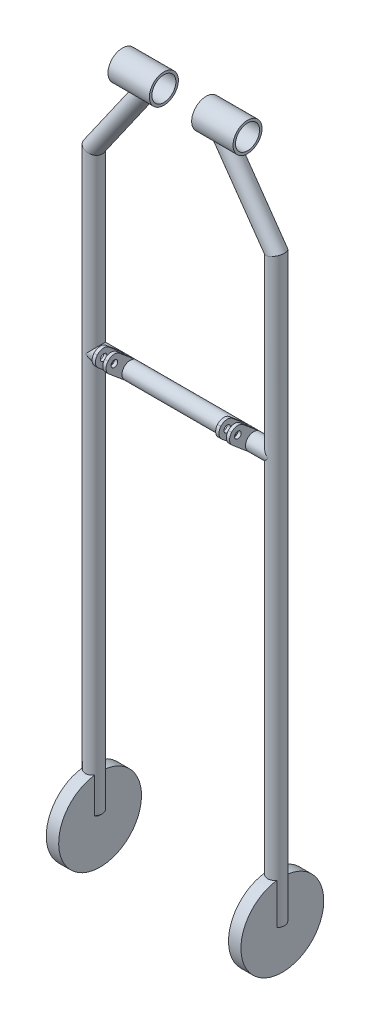
SolidWorks part; units mm, degrees
ref_plane "Alzado" through (0, 0, 0) normal (0, 0, 1) x (1, 0, 0)
ref_plane "Planta" through (0, 0, 0) normal (0, 1, 0) x (1, 0, 0)
ref_plane "Vista lateral" through (0, 0, 0) normal (1, 0, 0) x (0, 0, -1)
sketch "Croquis1" plane through (0, 0, 0) normal (1, 0, 0) x (0, 0, -1)
  circle A0 centre (0, 0) radius 17.5
  circle A1 centre (0, 0) radius 14.5
  dimension "D1" = 35
  dimension "D2" = 3
extrude "Saliente-Extruir1" add sketch "Croquis1" along normal blind 50
sketch "Croquis2" plane through (0, 0, 0) normal (0, 0, 1) x (1, 0, 0)
  line L0 (25, -17.5) -> (-34.5176, -102.5)
  line L1 (-34.5176, -102.5) -> (-34.5176, -802.5)
  line L2 (-34.5176, -102.5) -> (29.5486, -102.5) construction
  line L3 (25, 17.5) -> (25, -17.5) construction
  line L4 (50, 17.5) -> (0, 17.5) construction
  line L5 (0, -17.5) -> (50, -17.5) construction
  line L6 (0, 0) -> (50, 0) construction
  line L7 (50, -17.5) -> (50, 17.5) construction
  dimension "D1" = 85
  dimension "D2" = 700
  dimension "D3" = 55
  dimension "D4" = 64.0663
ref_plane "Plano1" through (25, -17.5, 0) normal (-0.5736, -0.8192, 0) x (0, 0, 1)
sketch "Croquis3" plane through (25, -17.5, 0) normal (-0.5736, -0.8192, 0) x (0, 0, 1)
  circle A0 centre (0, 0) radius 10
  circle A1 centre (0, 0) radius 7
  dimension "D2" = 3
  dimension "D1" = 20
sweep "Barrer1" add profiles "Croquis3" path "Croquis2"
sketch "Croquis4" plane through (50, 0, 0) normal (1, 0, 0) x (0, 0, -1)
  circle A0 centre (0, 0) radius 14.5 construction
  circle A1 centre (0, 0) radius 14.5
extrude "Cortar-Extruir1" cut sketch "Croquis4" against normal through all
sketch "Croquis5" plane through (0.0024, 0.0035, 0) normal (0.5736, 0.8192, 0) x (0.8192, -0.5736, 0)
  arc A4 (40.5164, 0) -> (26.1673, 9.0048) centre (30.5164, 0) ccw
  arc A5 (37.5164, 0) -> (28.2476, 6.6221) centre (30.5164, 0) ccw
  arc A6 (28.2476, -6.6221) -> (37.5164, 0) centre (30.5164, 0) ccw
  arc A7 (26.1673, -9.0048) -> (40.5164, 0) centre (30.5164, 0) ccw
  arc A8 (40.5164, 0) -> (26.1673, 9.0048) centre (30.5164, 0) ccw
  arc A9 (37.5164, 0) -> (28.2476, 6.6221) centre (30.5164, 0) ccw
  arc A10 (28.2476, -6.6221) -> (37.5164, 0) centre (30.5164, 0) ccw
  arc A11 (26.1673, -9.0048) -> (40.5164, 0) centre (30.5164, 0) ccw
  ellipse E2 centre (0.0061, 0) end of major axis (-30.5042, 0) minor radius 17.5 (28.2476, 6.6221) -> (26.1673, 9.0048) ccw
  ellipse E3 centre (0.0061, 0) end of major axis (-30.5042, 0) minor radius 17.5 (26.1673, -9.0048) -> (28.2476, -6.6221) ccw
  ellipse E4 centre (0.0061, 0) end of major axis (-30.5042, 0) minor radius 17.5 (28.2476, 6.6221) -> (26.1673, 9.0048) ccw
  ellipse E5 centre (0.0061, 0) end of major axis (-30.5042, 0) minor radius 17.5 (26.1673, -9.0048) -> (28.2476, -6.6221) ccw
  dimension "D1" = 0
extrude "Saliente-Extruir2" add sketch "Croquis5" along normal up to body separate body
ref_plane "Plano3" through (101, 0, 0) normal (1, 0, 0) x (0, 0, -1)
sketch "Croquis6" plane through (101, 0, 0) normal (1, 0, 0) x (0, 0, -1)
  circle A0 centre (0, 0) radius 14.5 construction
  circle A1 centre (0, 0) radius 17.5 construction
  circle A2 centre (0, 0) radius 14.5
  circle A3 centre (0, 0) radius 17.5
extrude "Saliente-Extruir3" add sketch "Croquis6" along normal blind 50 separate body
sketch "Croquis7" plane through (0, 0, 0) normal (0, 0, 1) x (1, 0, 0)
  line L0 (151, -17.5) -> (151, 17.5) construction
  line L1 (101, -17.5) -> (151, -17.5) construction
  line L2 (101, 17.5) -> (101, -17.5) construction
  line L3 (151, 17.5) -> (101, 17.5) construction
  line L4 (151, -17.5) -> (151, 17.5) construction
  line L5 (101, -17.5) -> (151, -17.5) construction
  line L6 (101, 17.5) -> (101, -17.5) construction
  line L7 (151, 17.5) -> (101, 17.5) construction
  line L8 (126, -17.5) -> (185.5176, -102.5)
  line L9 (185.5176, -102.5) -> (185.5176, -802.5)
  line L10 (185.5176, -102.5) -> (99.3833, -102.5) construction
  dimension "D1" = 85
  dimension "D2" = 700
  dimension "D3" = 86.1343
  dimension "D4" = 55
ref_plane "Plano4" through (126, -17.5, 0) normal (0.5736, -0.8192, 0) x (-0.8192, -0.5736, 0)
sketch "Croquis8" plane through (126, -17.5, 0) normal (0.5736, -0.8192, 0) x (-0.8192, -0.5736, 0)
  circle A0 centre (0, 0) radius 10
  circle A1 centre (0, 0) radius 7
  dimension "D2" = 3
  dimension "D1" = 20
sweep "Barrer2" add profiles "Croquis8" path "Croquis7"
sketch "Croquis9" plane through (49.675, -70.9433, 0) normal (-0.5736, 0.8192, 0) x (0.8192, 0.5736, 0)
  arc A2 (95.4443, 6.6221) -> (95.4443, -6.6221) centre (93.1756, 0) ccw
  arc A3 (97.5246, 9.0048) -> (97.5246, -9.0048) centre (93.1756, 0) ccw
  arc A4 (95.4443, 6.6221) -> (95.4443, -6.6221) centre (93.1756, 0) ccw
  arc A5 (97.5246, 9.0048) -> (97.5246, -9.0048) centre (93.1756, 0) ccw
  ellipse E2 centre (123.6859, 0) end of major axis (93.1756, 0) minor radius 17.5 (97.5246, 9.0048) -> (95.4443, 6.6221) ccw
  ellipse E3 centre (123.6859, 0) end of major axis (93.1756, 0) minor radius 17.5 (95.4443, -6.6221) -> (97.5246, -9.0048) ccw
  ellipse E4 centre (123.6859, 0) end of major axis (93.1756, 0) minor radius 17.5 (97.5246, 9.0048) -> (95.4443, 6.6221) ccw
  ellipse E5 centre (123.6859, 0) end of major axis (93.1756, 0) minor radius 17.5 (95.4443, -6.6221) -> (97.5246, -9.0048) ccw
  dimension "D1" = 0
extrude "Saliente-Extruir4" add sketch "Croquis9" along normal up to surface up to face at (132.5056, -16.5721, 0.0091)
sketch "Croquis10" plane through (0, 0, 0) normal (1, 0, 0) x (0, 0, -1)
  line L0 (10, -102.5) -> (10, -14.3614) construction
  line L1 (-10, -14.3614) -> (-10, -102.5) construction
  line L2 (10, -802.5) -> (10, -102.5) construction
  line L3 (-10, -102.5) -> (-10, -802.5) construction
  line L4 (10, -102.5) -> (10, -14.3614) construction
  line L5 (-10, -14.3614) -> (-10, -102.5) construction
  line L6 (10, -802.5) -> (10, -102.5) construction
  line L7 (-10, -102.5) -> (-10, -802.5) construction
  line L10 (0, -802.5) -> (0, -11.7642) construction
  circle A0 centre (0, -314.3614) radius 10
  dimension "D2" = 20
  dimension "D1" = 300
extrude "Saliente-Extruir5" add sketch "Croquis10" along normal up to surface and the other way up to surface contours A0 up to face at (195.5176, -99.347, 0) other way up to face at (-44.5176, -99.347, 0)
sketch "Croquis11" plane through (0, -802.5, 0) normal (0, -1, 0) x (1, 0, 0)
  line L0 (-34.5176, 0) -> (-44.5176, 0)
  circle A0 centre (-34.5176, 0) radius 10 construction
  circle A1 centre (-34.5176, 0) radius 10 construction
ref_plane "Plano5" through (-34.5176, -802.5, 0) normal (-1, 0, 0) x (0, 0, 1)
sketch "Croquis12" plane through (-34.5176, -802.5, 0) normal (-1, 0, 0) x (0, 0, 1)
  line L0 (-10, 0) -> (10, 0) construction
  circle A0 centre (0, 0) radius 50
  dimension "D1" = 100
extrude "Saliente-Extruir6" add sketch "Croquis12" along normal mid plane 15
chamfer "Chaflán3" distance 7 angle 45 2 edges at (-25.1635, -802.5, -3.5355) (-25.1635, -802.5, 3.5355)
chamfer "Chaflán4" distance 7 angle 45 1 edges at (-44.5176, -802.5, 0)
sketch "Croquis13" plane through (0, -802.5, 0) normal (0, -1, 0) x (1, 0, 0)
  line L0 (185.5176, 0) -> (175.5176, 0) construction
  circle A0 centre (185.5176, 0) radius 10 construction
  circle A1 centre (185.5176, 0) radius 10 construction
ref_plane "Plano6" through (185.5176, -802.5, 0) normal (-1, 0, 0) x (0, 0, 1)
sketch "Croquis14" plane through (185.5176, -802.5, 0) normal (-1, 0, 0) x (0, 0, 1)
  arc A0 (-6.6144, 49.5606) -> (6.6144, 49.5606) centre (0, 0) ccw construction
  arc A1 (-6.6144, 49.5606) -> (6.6144, 49.5606) centre (0, 0) ccw
  circle A2 centre (0, 0) radius 50
extrude "Saliente-Extruir8" add sketch "Croquis14" along normal mid plane 15 contours A2
sketch "Croquis15" plane through (151, 0, 0) normal (1, 0, 0) x (0, 0, -1)
  circle A0 centre (0, 0) radius 14.5 construction
  circle A1 centre (0, 0) radius 14.5
extrude "Cortar-Extruir2" cut sketch "Croquis15" against normal through all contours A1
ref_plane "Plano7" through (75, 0, 0) normal (1, 0, 0) x (0, 0, -1)
sketch "Croquis16" plane through (75, 0, 0) normal (1, 0, 0) x (0, 0, -1)
  line L0 (0, -314.3614) -> (-26.8116, -291.8638)
  line L1 (0, -314.3614) -> (0, -264.3614) construction
  arc A0 (-10, -314.3614) -> (10, -314.3614) centre (0, -314.3614) ccw construction
  arc A1 (10, -314.3614) -> (-10, -314.3614) centre (0, -314.3614) ccw construction
  arc A2 (-10, -314.3614) -> (10, -314.3614) centre (0, -314.3614) ccw
  arc A3 (10, -314.3614) -> (-10, -314.3614) centre (0, -314.3614) ccw
  dimension "D1" = 50
  dimension "D2" = 50
  dimension "D3" = 35
ref_plane "Plano8" through (75, -291.8638, 26.8116) normal (0, 0.6428, 0.766) x (1, 0, 0)
sketch "Croquis17" plane through (75, -291.8638, 26.8116) normal (0, 0.6428, 0.766) x (1, 0, 0)
  line L0 (120.5176, -373.9359) -> (120.5176, 164.7106) construction
  line L1 (-119.5176, 164.7106) -> (-119.5176, -368.5735) construction
  line L2 (120.5176, -373.9359) -> (120.5176, 164.7106) construction
  line L3 (-119.5176, 164.7106) -> (-119.5176, -368.5735) construction
  line L4 (-101.8572, -10) -> (102.8572, -10) construction
  line L5 (102.8572, 10) -> (-101.8572, 10) construction
  line L6 (-101.8572, -10) -> (102.8572, -10) construction
  line L7 (102.8572, 10) -> (-101.8572, 10) construction
  line L8 (0.5, 10) -> (0.5, -10) construction
  line L9 (-82.5176, 10) -> (-78.5176, 10)
  line L10 (-82.5176, 10) -> (-82.5176, -10)
  line L11 (-82.5176, -10) -> (-78.5176, -10)
  line L12 (-78.5176, 10) -> (-78.5176, -10)
  line L13 (-82.5176, 10) -> (-78.5176, -10) construction
  line L14 (-82.5176, -10) -> (-78.5176, 10) construction
  line L15 (-65.6176, 10) -> (-69.6176, 10)
  line L16 (-65.6176, 10) -> (-65.6176, -10)
  line L17 (-65.6176, -10) -> (-69.6176, -10)
  line L18 (-69.6176, 10) -> (-69.6176, -10)
  line L19 (-65.6176, 10) -> (-69.6176, -10) construction
  line L20 (-65.6176, -10) -> (-69.6176, 10) construction
  line L21 (66.6176, 10) -> (70.6176, 10)
  line L22 (66.6176, 10) -> (66.6176, -10)
  line L23 (70.6176, 10) -> (70.6176, -10)
  line L24 (66.6176, -10) -> (70.6176, -10)
  line L25 (83.5176, -10) -> (79.5176, -10)
  line L26 (83.5176, 10) -> (79.5176, 10)
  line L27 (79.5176, 10) -> (79.5176, -10)
  line L28 (83.5176, 10) -> (83.5176, -10)
  point P12 (-80.5176, 0)
  point P17 (-67.6176, 0)
  dimension "D1" = 8.9
  dimension "D2" = 4
  dimension "D3" = 4
  dimension "D4" = 37
extrude "Saliente-Extruir10" add sketch "Croquis17" against normal up to body separate body contours L12 L11 L10 L9 | L16 L17 L18 L15 | L23 L24 L22 L21 | L27 L25 L28 L26
fillet "Redondeo1" radius 10 8 edges at (156.5176, -299.5243, 33.2394) (156.5176, -284.2034, 20.3837) (143.6176, -284.2034, 20.3837) (143.6176, -299.5243, 33.2394) (-5.5176, -299.5243, 33.2394) (-5.5176, -284.2034, 20.3837) (7.3824, -284.2034, 20.3837) (7.3824, -299.5243, 33.2394)
sketch "Croquis18" plane through (158.5176, 0, 0) normal (1, 0, 0) x (0, 0, -1)
  line L0 (0, -314.3614) -> (-26.8116, -291.8638) construction
  circle A0 centre (-19.1511, -298.2917) radius 4
  arc A2 (-26.8116, -291.8638) -> (-25.579, -305.9522) centre (-19.1511, -298.2917) ccw construction
  dimension "D1" = 8
extrude "Cortar-Extruir3" cut sketch "Croquis18" against normal through all
equation "\"Diam_Tubo\"=35"
equation "\"D1@Croquis1\"=\"Diam_Tubo\""
equation "\"Grosor_Tubo\"=3"
equation "\"D2@Croquis1\"=\"Grosor_Tubo\""
equation "\"Dist_Sec\"=85"
equation "\"D1@Croquis2\"=\"Dist_Sec\""
equation "\"Diste_sec\" = 700"
equation "\"D2@Croquis2\"=\"Diste_sec\""
equation "\"Inclinacion_Princ\"= 55"
equation "\"D3@Croquis2\"=\"Inclinacion_Princ\""
equation "\"D2@Croquis3\"=\"Grosor_Tubo\""
equation "\"Diam_Tubo2\"=20"
equation "\"D1@Croquis3\"=\"Diam_Tubo2\""
equation "\"Ext_Tubo\"= 50"
equation "\"D1@Saliente-Extruir1\"=\"Ext_Tubo\""
equation "\"D1@Saliente-Extruir3\"=\"Ext_Tubo\""
equation "\"D1@Croquis7\"=\"Dist_Sec\""
equation "\"D2@Croquis7\"=\"Diste_sec\""
equation "\"D4@Croquis7\"=\"Inclinacion_Princ\""
equation "\"D1@Croquis8\"=\"Diam_Tubo2\""
equation "\"D2@Croquis8\"=\"Grosor_Tubo\""
equation "\"Dist_Soporte_Amortiguador\" = 300"
equation "\"D2@Croquis10\"=\"Diam_Tubo2\""
equation "\"Ext_Sop_Rueda\"=15"
equation "\"D1@Saliente-Extruir6\"=\"Ext_Sop_Rueda\""
equation "\"Tubo_Rueda\" = 100"
equation "\"D1@Saliente-Extruir8\"=\"Ext_Sop_Rueda\""
equation "\"Ang_Perp_SopAmort\"=50"
equation "\"D2@Croquis16\"=\"Ang_Perp_SopAmort\""
equation "\"Largo_SopAmort\"= 35"
equation "\"D3@Croquis16\"=\"Largo_SopAmort\""
equation "\"Dist_Entre_SopAmort\"= 8.9"
equation "\"D1@Croquis17\"=\"Dist_Entre_SopAmort\""
equation "\"Grosor_SopAmort\"=4"
equation "\"D2@Croquis17\"=\"Grosor_SopAmort\""
equation "\"D3@Croquis17\"=\"Grosor_SopAmort\""
equation "\"Dist_SopRu_SopAmort\"=36.881"
equation "\"Agujero_Amort\"=8"
equation "\"D1@Croquis18\"=\"Agujero_Amort\""
equation "\"D1@Croquis10\"=\"Dist_Soporte_Amortiguador\""
equation "\"D1@Croquis12\"=\"Tubo_Rueda\""
